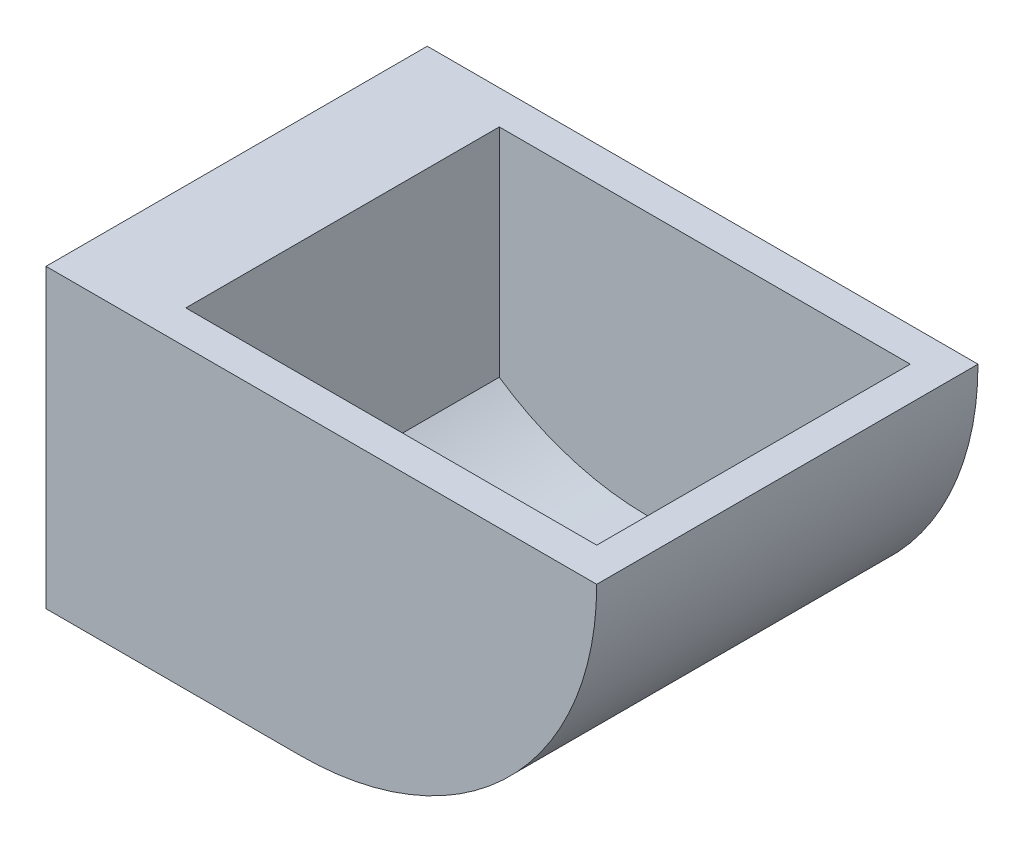
SolidWorks part; units mm, degrees
ref_plane "Front Plane" through (0, 0, 0) normal (0, 0, 1) x (1, 0, 0)
ref_plane "Top Plane" through (0, 0, 0) normal (0, 1, 0) x (1, 0, 0)
ref_plane "Right Plane" through (0, 0, 0) normal (1, 0, 0) x (0, 0, -1)
sketch "Sketch1" plane through (0, 0, 0) normal (0, 0, 1) x (1, 0, 0)
  line L0 (-35, 0) -> (35, 0)
  circle A0 centre (0, 0) radius 35
  dimension "D1" = 70
extrude "Boss-Extrude1" add sketch "Sketch1" along normal blind 45 contours L0 A0 region at (0, -14.8545, 0)
sketch "Sketch2" plane through (0, 0, 0) normal (0, 1, 0) x (1, 0, 0)
  line L0 (-35, 0) -> (35, 0) construction
  line L1 (-31, -4) -> (0.5147, -4)
  line L2 (-31, -4) -> (-31, -41)
  line L3 (-31, -41) -> (0, -41)
  line L5 (-35, -45) -> (35, -45) construction
  line L6 (-35, -45) -> (-35, 0) construction
  line L7 (0, 0) -> (0, -45) construction
  line L8 (-31, -4) -> (0.5147, -4)
  line L9 (-31, -4) -> (-31, -41)
  line L10 (-31, -41) -> (0, -41)
  line L13 (-31, -4) -> (0, -4)
  line L14 (-31, -4) -> (-31, -41)
  line L15 (-31, -41) -> (0, -41)
  line L16 (0, -4) -> (0, -41)
  dimension "D1" = 4
  dimension "D2" = 4
  dimension "D3" = 4
ref_axis "Axis1" through (0, 0, 45) along (0, 0, -1)
revolve "Cut-Revolve1" cut sketch "Sketch2" angle 360 about L7 region at (-15.5, 0, 22.5)
sketch "Sketch3" plane through (0, 0, 45) normal (0, 0, 1) x (1, 0, 0)
  line L0 (-17.5, 0) -> (-17.5, -35)
  line L1 (0, 0) -> (-35, 0)
  line L4 (0, 0) -> (0, -35)
  line L9 (-35, -35) -> (-17.5, -35)
  line L10 (-35, 0) -> (-35, -35)
  line L11 (-35, 0) -> (-17.5, 0)
  line L12 (-35, -35) -> (0, -35)
  line L13 (-35, 0) -> (-35, -35)
  arc A0 (-35, 0) -> (35, 0) centre (0, 0) ccw construction
  line M1 (35, 0) -> (-35, 0)
  arc M2 (-35, 0) -> (35, 0) centre (0, 0) ccw
extrude "Boss-Extrude3" add sketch "Sketch3" against normal blind 45 contours L10 L9 L0 M2 | L0 L12 M2 | L0 M1 M2 region at (-24.6757, -11.8721, 45) region at (-13.1858, -33.611, 45) region at (-28.7561, -26.4591, 45)
sketch "Sketch4" plane through (-35, 0, 0) normal (-1, 0, 0) x (0, 0, 1)
  line L0 (0, -35) -> (45, -35) construction
  line L2 (0, 0) -> (0, -35) construction
  line L3 (0, 0) -> (45, 0) construction
  line L4 (45, 0) -> (22.5, 0) construction
  line L5 (22.5, 0) -> (22.5, -35) construction
  circle A0 centre (10, -17.5) radius 5.15
  circle A1 centre (35, -17.5) radius 5.15
  dimension "D1" = 10.3
  dimension "D2" = 17.5
  dimension "D3" = 10
extrude "Cut-Extrude1" cut sketch "Sketch4" against normal blind 12
sketch "Sketch5" plane through (0, 0, 0) normal (0, 0, -1) x (-1, 0, 0)
  line L0 (35, -35) -> (0, -35) construction
  line L1 (35, 0) -> (30, 0)
  line L2 (35, 0) -> (35, -35)
  line L3 (35, -35) -> (30, -35)
  line L4 (30, 0) -> (30, -35)
  dimension "D1" = 5
extrude "Cut-Extrude2" cut sketch "Sketch5" against normal through all
